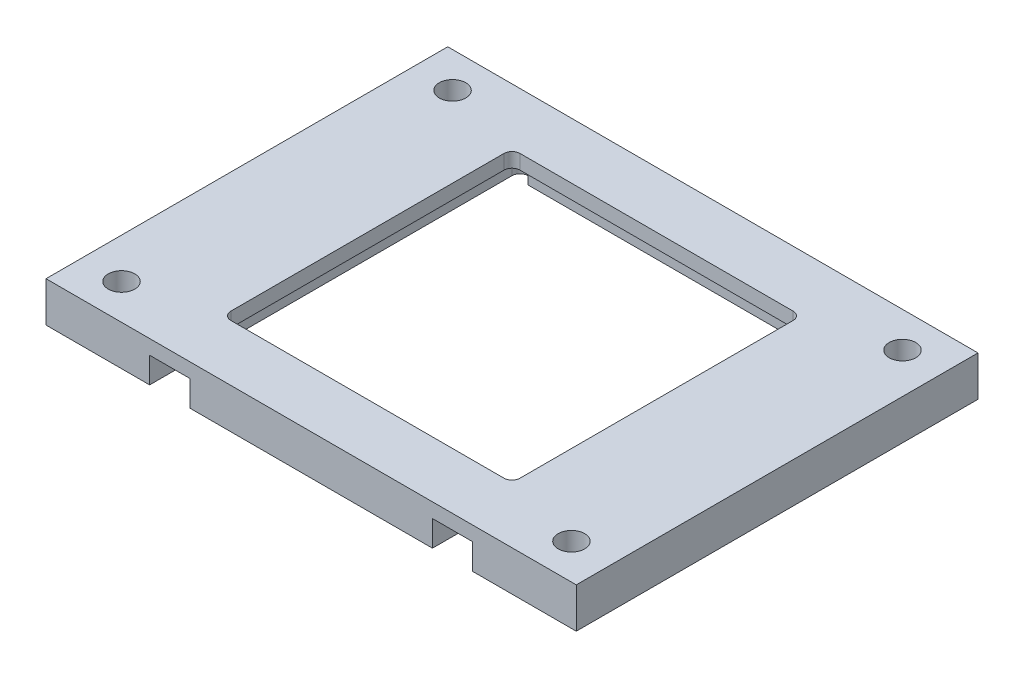
SolidWorks part; units mm, degrees
ref_plane "Front Plane" through (0, 0, 0) normal (0, 0, 1) x (1, 0, 0)
ref_plane "Top Plane" through (0, 0, 0) normal (0, 1, 0) x (1, 0, 0)
ref_plane "Right Plane" through (0, 0, 0) normal (1, 0, 0) x (0, 0, -1)
sketch "Sketch1" plane through (0, 0, 0) normal (0, 1, 0) x (1, 0, 0)
  line L0 (20.1, -20.1) -> (20.1, 21.1)
  line L1 (-20.1, -20.1) -> (20.1, -20.1)
  line L3 (-18.1, 20.1) -> (18.1, 20.1)
  line L5 (-20.1, 21.1) -> (-20.1, -20.1)
  line L7 (-33, -25) -> (33, -25)
  line L8 (-33, -25) -> (-33, 25)
  line L9 (-33, 25) -> (33, 25)
  line L10 (33, -25) -> (33, 25)
  line L11 (-33, -25) -> (33, 25) construction
  line L12 (-33, 25) -> (33, -25) construction
  line L15 (-20.1, 21.1) -> (-18.1, 21.1)
  line L16 (-18.1, 20.1) -> (-18.1, 21.1)
  line L19 (20.1, 21.1) -> (18.1, 21.1)
  line L20 (18.1, 20.1) -> (18.1, 21.1)
  circle A0 centre (-28, 20.6) radius 1.65
  circle A1 centre (28, 20.6) radius 1.65
  circle A2 centre (-28, -20.6) radius 1.65
  circle A3 centre (28, -20.6) radius 1.65
  point P0 (0, 0)
  point P15 (0, 0)
  dimension "D3" = 20.6
  dimension "D4" = 20.6
  dimension "D5" = 20.6
  dimension "D6" = 20.6
  dimension "D7" = 28
  dimension "D10" = 28
  dimension "D11" = 3.3
  dimension "D14" = 2
  dimension "D2" = 40.2
  dimension "D8" = 28
  dimension "D9" = 28
  dimension "D12" = 66
  dimension "D13" = 50
  dimension "D15" = 1
  dimension "D16" = 2
  dimension "D17" = 1
  dimension "D18" = 20.1
  dimension "D19" = 40.2
  dimension "D20" = 20.1
extrude "Boss-Extrude1" add sketch "Sketch1" along normal blind 5
sketch "Sketch2" plane through (0, 5, 0) normal (0, 1, 0) x (1, 0, 0)
  line L12 (-18, -18) -> (18, -18)
  line L13 (18, -18) -> (18, 18)
  line L14 (-18, 18) -> (-18, -18)
  line L15 (18, 18) -> (-18, 18)
  line L54 (-20.1, 21.1) -> (-20.1, -20.1)
  line L55 (-20.1, -20.1) -> (20.1, -20.1)
  line L56 (20.1, -20.1) -> (20.1, 21.1)
  line L57 (20.1, 21.1) -> (18.1, 21.1)
  line L58 (18.1, 21.1) -> (18.1, 20.1)
  line L59 (18.1, 20.1) -> (-18.1, 20.1)
  line L60 (-18.1, 20.1) -> (-18.1, 21.1)
  line L61 (-18.1, 21.1) -> (-20.1, 21.1)
  line L62 (-20.1, 21.1) -> (-20.1, -20.1)
  line L63 (-20.1, -20.1) -> (20.1, -20.1)
  line L64 (20.1, -20.1) -> (20.1, 21.1)
  line L65 (20.1, 21.1) -> (18.1, 21.1)
  line L66 (18.1, 21.1) -> (18.1, 20.1)
  line L67 (18.1, 20.1) -> (-18.1, 20.1)
  line L68 (-18.1, 20.1) -> (-18.1, 21.1)
  line L69 (-18.1, 21.1) -> (-20.1, 21.1)
  dimension "D1" = 36
  dimension "D3" = 36
  dimension "D4" = 18
  dimension "D5" = 18
  dimension "D6" = 36
  dimension "D7" = 36
  dimension "D2" = 0
extrude "Boss-Extrude2" add sketch "Sketch2" against normal blind 1.8
sketch "Sketch3" plane through (0, 0, 25) normal (0, 0, 1) x (1, 0, 0)
  line L0 (-33, 0) -> (33, 0) construction
  line L1 (-20.1, 0) -> (-15.1, 0)
  line L3 (-20.1, 3.2) -> (-15.1, 3.2)
  line L4 (-15.1, 0) -> (-15.1, 3.2)
  line L5 (20.1, 0) -> (20.1, 3.2)
  line L6 (20.1, 0) -> (15.1, 0)
  line L8 (20.1, 3.2) -> (15.1, 3.2)
  line L9 (15.1, 0) -> (15.1, 3.2)
  line L10 (-20.1, 0) -> (-20.1, 3.2)
  dimension "D1" = 5
  dimension "D2" = 5
  dimension "D3" = 0
  dimension "D4" = 0
  dimension "D5" = 3.2
  dimension "D6" = 3.2
extrude "Cut-Extrude1" cut sketch "Sketch3" against normal up to next
fillet "Fillet1" radius 1 8 edges at (-18, 4.1, 18) (18, 4.1, 18) (18, 4.1, -18) (-18, 4.1, -18) (-20.1, 1.6, -21.1) (-18.1, 1.6, -21.1) (18.1, 1.6, -21.1) (20.1, 1.6, -21.1)
